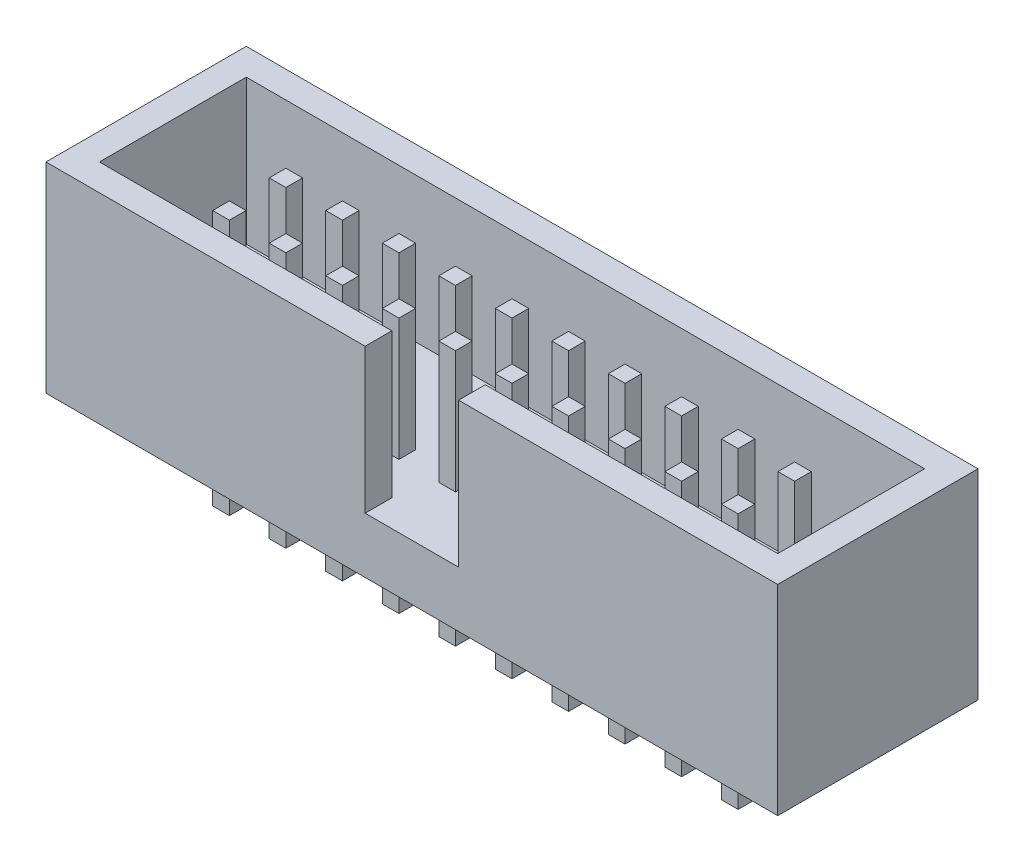
SolidWorks part; units mm, degrees
ref_plane "前视基准面" through (0, 0, 0) normal (0, 0, 1) x (1, 0, 0)
ref_plane "上视基准面" through (0, 0, 0) normal (0, 1, 0) x (1, 0, 0)
ref_plane "右视基准面" through (0, 0, 0) normal (1, 0, 0) x (0, 0, -1)
sketch "草图1" plane through (0, 0, 0) normal (0, 1, 0) x (1, 0, 0)
  line L0 (0, 85.0964) -> (0, -118.2031) construction
  line L1 (-16.44, 4.5) -> (16.44, 4.5)
  line L2 (-16.44, 4.5) -> (-16.44, -4.5)
  line L3 (-16.44, -4.5) -> (16.44, -4.5)
  line L4 (16.44, 4.5) -> (16.44, -4.5)
  line L5 (-200.5452, 0) -> (261.2352, 0) construction
  dimension "D1" = 9
  dimension "D2" = 32.88
extrude "拉伸1" add sketch "草图1" along normal blind 9
sketch "草图2" plane through (0, 9, 0) normal (0, 1, 0) x (-1, 0, 0)
  line L8 (-15.24, 3.3) -> (-15.24, -3.3)
  line L9 (15.24, 3.3) -> (-15.24, 3.3)
  line L10 (15.24, -3.3) -> (15.24, 3.3)
  line L11 (-15.24, -3.3) -> (15.24, -3.3)
  line L12 (-15.24, 3.3) -> (-15.24, -3.3)
  line L13 (15.24, 3.3) -> (-15.24, 3.3)
  line L14 (15.24, -3.3) -> (15.24, 3.3)
  line L15 (-15.24, -3.3) -> (15.24, -3.3)
  dimension "D1" = 1.2
extrude "切除-拉伸1" cut sketch "草图2" against normal blind 6.5
sketch "草图3" plane through (0, 0, 4.5) normal (0, 0, 1) x (1, 0, 0)
  line L0 (-16.44, 9) -> (16.44, 9) construction
  line L1 (-2.1, 9) -> (2.1, 9)
  line L2 (-2.1, 9) -> (-2.1, 2.5)
  line L3 (-2.1, 2.5) -> (2.1, 2.5)
  line L4 (2.1, 9) -> (2.1, 2.5)
  line L5 (-15.24, 2.5) -> (15.24, 2.5) construction
  line L6 (0, 9.4226) -> (0, -4.0288) construction
  dimension "D1" = 4.2
extrude "切除-拉伸2" cut sketch "草图3" against normal blind 6.5
sketch "草图5" plane through (0, 0, 0) normal (0, -1, 0) x (1, 0, 0)
  line L0 (0, 6.0683) -> (0, -6.9786) construction
  line L1 (-14.7999, 0) -> (15.2382, 0) construction
  line L2 (-1.27, 2.5244) -> (-1.27, -0.4442) construction
  line L3 (-1.645, 0.895) -> (-0.895, 0.895)
  line L4 (-1.645, 0.895) -> (-1.645, 1.645)
  line L5 (-1.645, 1.645) -> (-0.895, 1.645)
  line L6 (-0.895, 0.895) -> (-0.895, 1.645)
  line L7 (-2.3518, 1.27) -> (0.5396, 1.27) construction
  line L8 (0.895, 0.895) -> (1.645, 0.895)
  line L9 (0.895, 0.895) -> (0.895, 1.645)
  line L10 (0.895, 1.645) -> (1.645, 1.645)
  line L11 (1.645, 0.895) -> (1.645, 1.645)
  line L12 (3.435, 0.895) -> (4.185, 0.895)
  line L13 (3.435, 0.895) -> (3.435, 1.645)
  line L14 (3.435, 1.645) -> (4.185, 1.645)
  line L15 (4.185, 0.895) -> (4.185, 1.645)
  line L16 (5.975, 0.895) -> (6.725, 0.895)
  line L17 (5.975, 0.895) -> (5.975, 1.645)
  line L18 (5.975, 1.645) -> (6.725, 1.645)
  line L19 (6.725, 0.895) -> (6.725, 1.645)
  line L20 (8.515, 0.895) -> (9.265, 0.895)
  line L21 (8.515, 0.895) -> (8.515, 1.645)
  line L22 (8.515, 1.645) -> (9.265, 1.645)
  line L23 (9.265, 0.895) -> (9.265, 1.645)
  line L24 (11.055, 0.895) -> (11.805, 0.895)
  line L25 (11.055, 0.895) -> (11.055, 1.645)
  line L26 (11.055, 1.645) -> (11.805, 1.645)
  line L27 (11.805, 0.895) -> (11.805, 1.645)
  line L32 (0.895, -1.645) -> (1.645, -1.645)
  line L33 (0.895, -1.645) -> (0.895, -0.895)
  line L34 (0.895, -0.895) -> (1.645, -0.895)
  line L35 (1.645, -1.645) -> (1.645, -0.895)
  line L36 (3.435, -1.645) -> (4.185, -1.645)
  line L37 (3.435, -1.645) -> (3.435, -0.895)
  line L38 (3.435, -0.895) -> (4.185, -0.895)
  line L39 (4.185, -1.645) -> (4.185, -0.895)
  line L40 (5.975, -1.645) -> (6.725, -1.645)
  line L41 (5.975, -1.645) -> (5.975, -0.895)
  line L42 (5.975, -0.895) -> (6.725, -0.895)
  line L43 (6.725, -1.645) -> (6.725, -0.895)
  line L44 (8.515, -1.645) -> (9.265, -1.645)
  line L45 (8.515, -1.645) -> (8.515, -0.895)
  line L46 (8.515, -0.895) -> (9.265, -0.895)
  line L47 (9.265, -1.645) -> (9.265, -0.895)
  line L48 (11.055, -1.645) -> (11.805, -1.645)
  line L49 (11.055, -1.645) -> (11.055, -0.895)
  line L50 (11.055, -0.895) -> (11.805, -0.895)
  line L51 (11.805, -1.645) -> (11.805, -0.895)
  line L54 (-4.185, 0.895) -> (-3.435, 0.895)
  line L55 (-4.185, 0.895) -> (-4.185, 1.645)
  line L56 (-4.185, 1.645) -> (-3.435, 1.645)
  line L57 (-3.435, 0.895) -> (-3.435, 1.645)
  line L58 (-6.725, 0.895) -> (-5.975, 0.895)
  line L59 (-6.725, 0.895) -> (-6.725, 1.645)
  line L60 (-6.725, 1.645) -> (-5.975, 1.645)
  line L61 (-5.975, 0.895) -> (-5.975, 1.645)
  line L62 (-9.265, 0.895) -> (-8.515, 0.895)
  line L63 (-9.265, 0.895) -> (-9.265, 1.645)
  line L64 (-9.265, 1.645) -> (-8.515, 1.645)
  line L65 (-8.515, 0.895) -> (-8.515, 1.645)
  line L66 (-11.805, 0.895) -> (-11.055, 0.895)
  line L67 (-11.805, 0.895) -> (-11.805, 1.645)
  line L68 (-11.805, 1.645) -> (-11.055, 1.645)
  line L69 (-11.055, 0.895) -> (-11.055, 1.645)
  line L70 (-1.645, -1.645) -> (-0.895, -1.645)
  line L71 (-1.645, -1.645) -> (-1.645, -0.895)
  line L72 (-1.645, -0.895) -> (-0.895, -0.895)
  line L73 (-0.895, -1.645) -> (-0.895, -0.895)
  line L74 (-4.185, -1.645) -> (-3.435, -1.645)
  line L75 (-4.185, -1.645) -> (-4.185, -0.895)
  line L76 (-4.185, -0.895) -> (-3.435, -0.895)
  line L77 (-3.435, -1.645) -> (-3.435, -0.895)
  line L78 (-6.725, -1.645) -> (-5.975, -1.645)
  line L79 (-6.725, -1.645) -> (-6.725, -0.895)
  line L80 (-6.725, -0.895) -> (-5.975, -0.895)
  line L81 (-5.975, -1.645) -> (-5.975, -0.895)
  line L82 (-9.265, -1.645) -> (-8.515, -1.645)
  line L83 (-9.265, -1.645) -> (-9.265, -0.895)
  line L84 (-9.265, -0.895) -> (-8.515, -0.895)
  line L85 (-8.515, -1.645) -> (-8.515, -0.895)
  line L86 (-11.805, -1.645) -> (-11.055, -1.645)
  line L87 (-11.805, -1.645) -> (-11.805, -0.895)
  line L88 (-11.805, -0.895) -> (-11.055, -0.895)
  line L89 (-11.055, -1.645) -> (-11.055, -0.895)
  line L92 (-1.645, -1.645) -> (-0.895, -1.645) [skipped]
  line L93 (-0.895, -1.645) -> (-0.895, -0.895) [skipped]
  line L94 (-1.645, -0.895) -> (-0.895, -0.895) [skipped]
  line L95 (-1.645, -1.645) -> (-1.645, -0.895) [skipped]
  dimension "D1" = 0.75
  dimension "D2" = 0.75
  dimension "D3" = 1.27
  dimension "D4" = 1.27
extrude "拉伸2" add sketch "草图5" along normal blind 3.5 and the other way offset from surface 1 other way up to face at (0, 9, 1.3)
